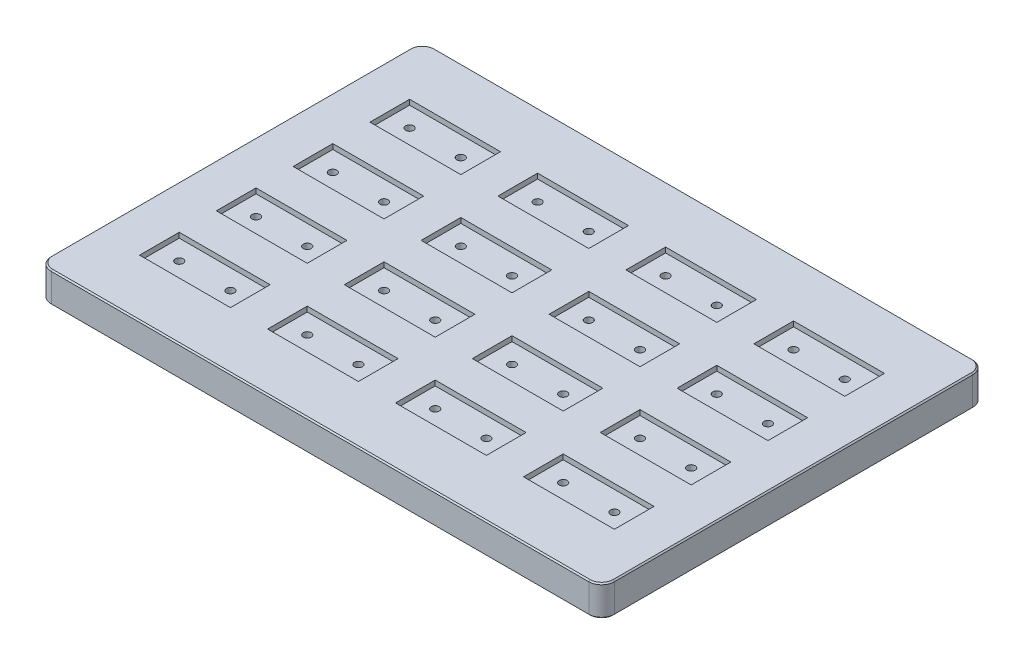
SolidWorks part; units mm, degrees
ref_plane "Front Plane" through (0, 0, 0) normal (0, 0, 1) x (1, 0, 0)
ref_plane "Top Plane" through (0, 0, 0) normal (0, 1, 0) x (1, 0, 0)
ref_plane "Right Plane" through (0, 0, 0) normal (1, 0, 0) x (0, 0, -1)
sketch "Sketch1" plane through (0, 0, 0) normal (0, 1, 0) x (1, 0, 0)
  line L1 (0, 0) -> (220, 0)
  line L2 (0, 0) -> (0, 150)
  line L3 (0, 150) -> (220, 150)
  line L4 (220, 0) -> (220, 150)
  dimension "D1" = 220
  dimension "D2" = 150
extrude "Boss-Extrude1" add sketch "Sketch1" along normal blind 12
sketch "Sketch2" plane through (0, 12, 0) normal (0, 1, 0) x (1, 0, 0)
  line L2 (0, 150) -> (0, 0) construction
  line L3 (17.25, 37.75) -> (52.75, 37.75)
  line L4 (17.25, 37.75) -> (17.25, 22.25)
  line L5 (17.25, 22.25) -> (52.75, 22.25)
  line L6 (52.75, 37.75) -> (52.75, 22.25)
  line L7 (0, 0) -> (220, 0) construction
  dimension "D1" = 15.5
  dimension "D2" = 35.5
  dimension "D3" = 17.25
  dimension "D4" = 22.25
extrude "Cut-Extrude1" cut sketch "Sketch2" against normal blind 2
pattern_linear "LPattern1" count 4 spacing 30 along (0, 0, -1) count 4 spacing 50 along (1, 0, 0) of "Cut-Extrude1"
sketch "Sketch3" plane through (0, 10, 0) normal (0, 1, 0) x (1, 0, 0)
  line L0 (35, 30) -> (35, 37.75) construction
  line L1 (35, 30) -> (52.75, 30) construction
  line L2 (52.75, 37.75) -> (17.25, 37.75) construction
  line L3 (52.75, 22.25) -> (52.75, 37.75) construction
  circle A0 centre (25, 30) radius 1.55
  circle A1 centre (45, 30) radius 1.55
  dimension "D1" = 3.1
  dimension "D2" = 20
extrude "Cut-Extrude2" cut sketch "Sketch3" against normal through all
pattern_linear "LPattern2" count 4 spacing 30 along (0, 0, -1) count 4 spacing 50 along (1, 0, 0) of "Cut-Extrude2"
sketch "Sketch4" plane through (0, 0, 0) normal (0, -1, 0) x (1, 0, 0)
  line L0 (0, -150) -> (0, 0) construction
  line L1 (10, -10) -> (210, -10)
  line L2 (10, -10) -> (10, -140)
  line L3 (10, -140) -> (210, -140)
  line L4 (210, -10) -> (210, -140)
  line L5 (220, -150) -> (0, -150) construction
  dimension "D1" = 200
  dimension "D2" = 130
  dimension "D3" = 10
  dimension "D4" = 10
extrude "Cut-Extrude3" cut sketch "Sketch4" against normal blind 3
fillet "Fillet1" radius 5 4 edges at (0, 6, -150) (0, 6, 0) (220, 6, 0) (220, 6, -150)
chamfer "Chamfer1" distance 0.5 angle 45 16 edges at (0, 0, -75) (1.4645, 0, -1.4645) (1.4645, 0, -148.5355) (110, 0, -150) (218.5355, 0, -1.4645) (218.5355, 0, -148.5355) (220, 0, -75) (0, 12, -75) (1.4645, 12, -1.4645) (1.4645, 12, -148.5355) (110, 12, 0) (110, 12, -150) (218.5355, 12, -1.4645) (218.5355, 12, -148.5355) (220, 12, -75) (110, 0, 0)
